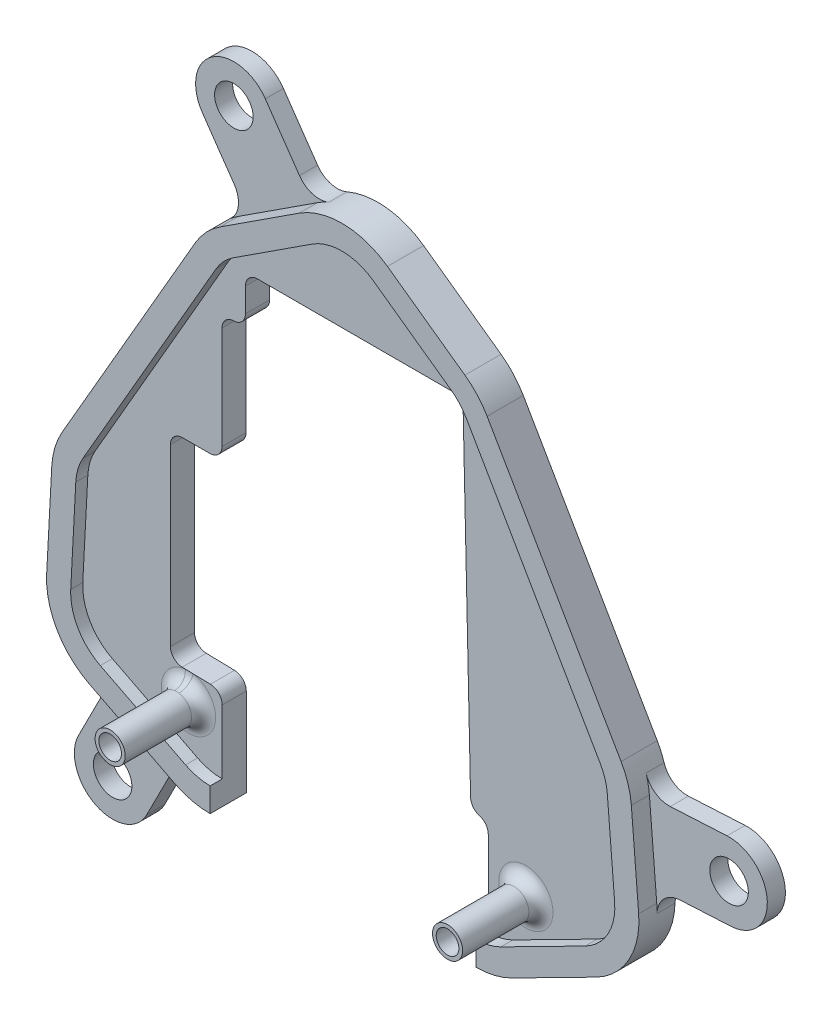
SolidWorks part; units mm, degrees
note: The reader was unsure of these and kept them because the rebuilt part matched: shared geometry of "Sketch2<4>", "Sketch2<7>".
ref_plane "Front" through (0, 0, 0) normal (0, 0, 1) x (1, 0, 0)
ref_plane "Top" through (0, 0, 0) normal (0, 1, 0) x (1, 0, 0)
ref_plane "Right" through (0, 0, 0) normal (1, 0, 0) x (0, 0, -1)
ref_plane "Plane1" through (0, 0, 5) normal (0, 0, 1) x (1, 0, 0)
sketch "Model" plane through (0, 0, 5) normal (0, 0, 1) x (1, 0, 0)
  line L0 (41.2744, 9.8256) -> (42.9744, 9.8256)
  line L1 (42.9744, 9.8256) -> (42.9744, 8.1256)
  line L2 (42.9744, 8.1256) -> (41.2744, 8.1256)
  line L3 (41.2744, 8.1256) -> (41.2744, 9.8256)
  line L4 (26.2031, 36.8727) -> (37.2177, 36.8727)
  line L5 (26.2031, 29.067) -> (26.2031, 36.8727)
  line L6 (26.2031, 29.067) -> (37.2177, 29.067)
  line L7 (37.2177, 29.067) -> (37.2177, 36.8727)
  line L8 (26.2031, 29.067) -> (26.2031, 36.8726)
  line L9 (26.2031, 36.8726) -> (37.2177, 36.8726)
  line L10 (37.2177, 36.8726) -> (37.2177, 29.067)
  line L11 (37.2177, 29.067) -> (26.2031, 29.067)
  line L12 (43.8871, 3.9834) -> (51.5741, 2.6279)
  line L13 (43.8871, 3.9834) -> (45.7997, 14.8306)
  line L14 (45.7997, 14.8306) -> (53.4867, 13.4752)
  line L15 (51.5741, 2.6279) -> (53.4867, 13.4752)
  line L16 (45.7997, 14.8306) -> (53.4868, 13.4752)
  line L17 (53.4868, 13.4752) -> (51.5741, 2.6279)
  line L18 (51.5741, 2.6279) -> (43.8871, 3.9834)
  line L19 (43.8871, 3.9834) -> (45.7997, 14.8306)
  line L20 (44.5033, 14.8869) -> (51.2631, 18.7897)
  line L21 (38.9959, 24.4258) -> (44.5033, 14.8869)
  line L22 (38.9959, 24.4258) -> (45.7558, 28.3286)
  line L23 (45.7558, 28.3286) -> (51.2631, 18.7897)
  line L24 (38.996, 24.4258) -> (45.7558, 28.3286)
  line L25 (45.7558, 28.3286) -> (51.2631, 18.7897)
  line L26 (51.2631, 18.7897) -> (44.5033, 14.8869)
  line L27 (44.5033, 14.8869) -> (38.996, 24.4258)
  line L28 (20.1071, -1.9033) -> (31.1217, -1.9033)
  line L29 (31.1217, -1.9033) -> (31.1217, 5.9022)
  line L30 (20.1071, 5.9022) -> (31.1217, 5.9022)
  line L31 (20.1071, -1.9033) -> (20.1071, 5.9022)
  line L32 (31.1217, 5.9022) -> (31.1217, -1.9033)
  line L33 (31.1217, -1.9033) -> (20.1071, -1.9033)
  line L34 (20.1071, -1.9033) -> (20.1071, 5.9023)
  line L35 (20.1071, 5.9023) -> (31.1217, 5.9022)
  line L36 (9.3055, 13.649) -> (16.9925, 15.0044)
  line L37 (16.9925, 15.0044) -> (18.9052, 4.1572)
  line L38 (11.2182, 2.8017) -> (18.9052, 4.1572)
  line L39 (9.3055, 13.649) -> (11.2182, 2.8017)
  line L40 (18.9052, 4.1571) -> (11.2182, 2.8017)
  line L41 (11.2182, 2.8017) -> (9.3055, 13.649)
  line L42 (9.3055, 13.649) -> (16.9925, 15.0044)
  line L43 (16.9925, 15.0044) -> (18.9052, 4.1571)
  line L44 (31.5611, -1.9033) -> (42.5757, -1.9033)
  line L45 (42.5757, -1.9033) -> (42.5757, 5.9022)
  line L46 (31.5611, 5.9022) -> (42.5757, 5.9022)
  line L47 (31.5611, -1.9033) -> (31.5611, 5.9022)
  line L48 (42.5757, 5.9022) -> (42.5757, -1.9033)
  line L49 (42.5757, -1.9033) -> (31.5611, -1.9033)
  line L50 (31.5611, -1.9033) -> (31.5611, 5.9023)
  line L51 (31.5611, 5.9023) -> (42.5757, 5.9022)
  line L52 (17.157, 27.6936) -> (23.9169, 23.7908)
  line L53 (18.4096, 14.2519) -> (23.9169, 23.7908)
  line L54 (11.6497, 18.1547) -> (18.4096, 14.2519)
  line L55 (11.6497, 18.1547) -> (17.157, 27.6936)
  line L56 (18.4096, 14.2519) -> (11.6497, 18.1547)
  line L57 (11.6497, 18.1547) -> (17.157, 27.6936)
  line L58 (17.157, 27.6936) -> (23.9169, 23.7908)
  line L59 (23.9169, 23.7908) -> (18.4096, 14.2519)
  line L60 (31.6641, -2.0303) -> (42.6787, -2.0303)
  line L61 (31.6641, -2.0303) -> (31.6641, 5.7752)
  line L62 (31.6641, 5.7752) -> (42.6787, 5.7752)
  line L63 (42.6787, -2.0303) -> (42.6787, 5.7752)
  line L64 (31.6641, 5.7752) -> (31.6641, -2.0303)
  line L65 (31.6641, -2.0303) -> (42.6787, -2.0303)
  line L66 (42.6787, -2.0303) -> (42.6787, 5.7753)
  line L67 (42.6787, 5.7753) -> (31.6641, 5.7752)
  line L68 (31.1217, -2.0304) -> (31.1217, 5.7752)
  line L69 (20.1071, 5.7752) -> (31.1217, 5.7752)
  line L70 (20.1071, -2.0304) -> (20.1071, 5.7752)
  line L71 (20.1071, -2.0304) -> (31.1217, -2.0304)
  line L72 (20.1071, 5.7752) -> (20.1071, -2.0304)
  line L73 (20.1071, -2.0304) -> (31.1217, -2.0304)
  line L74 (31.1217, -2.0304) -> (31.1217, 5.7752)
  line L75 (31.1217, 5.7752) -> (20.1071, 5.7752)
  line L76 (38.0604, 30.1846) -> (38.0604, 31.7086)
  line L77 (38.0604, 31.7086) -> (39.5844, 31.7086)
  line L78 (39.5844, 31.7086) -> (39.5844, 30.1846)
  line L79 (39.5844, 30.1846) -> (38.0604, 30.1846)
  line L80 (23.2104, 9.8646) -> (23.2104, 11.3886)
  line L81 (23.2104, 11.3886) -> (24.7344, 11.3886)
  line L82 (24.7344, 11.3886) -> (24.7344, 9.8646)
  line L83 (24.7344, 9.8646) -> (23.2104, 9.8646)
  line L84 (11.4952, 2.039) -> (18.4997, -1.5242)
  line L85 (10.454, 15.0927) -> (21.5718, 34.3494)
  line L86 (9.3219, 5.9287) -> (9.9312, 13.4171)
  line L87 (22.7072, 35.6017) -> (29.1341, 40.2036)
  line L88 (20.3133, -1.9589) -> (42.3955, -1.9589)
  line L89 (33.6436, 40.3046) -> (40.1911, 36.0465)
  line L90 (44.2091, -1.5242) -> (51.2858, 2.0757)
  line L91 (53.0458, 13.7815) -> (53.4666, 5.8529)
  line L92 (41.4745, 34.6932) -> (52.5155, 15.5695)
  circle A0 centre (31.7104, 23.1996) radius 1.4
  circle A1 centre (31.7104, 15.1997) radius 1.4
  circle A2 centre (42.1244, 16.5956) radius 0.85
  circle A3 centre (42.1244, 14.0556) radius 0.85
  circle A4 centre (42.1244, 11.5156) radius 0.85
  circle A5 centre (42.1244, 6.4356) radius 0.85
  circle A6 centre (26.2031, 36.8727) radius 0.0381
  circle A7 centre (37.2177, 36.8727) radius 0.0381
  circle A8 centre (26.2031, 29.067) radius 0.0381
  circle A9 centre (26.2031, 36.8727) radius 0.0381
  circle A10 centre (26.2031, 29.067) radius 0.0381
  circle A11 centre (37.2177, 29.067) radius 0.0381
  circle A12 centre (37.2177, 29.067) radius 0.0381
  circle A13 centre (37.2177, 36.8727) radius 0.0381
  circle A14 centre (43.8871, 3.9834) radius 0.0381
  circle A15 centre (51.5741, 2.6279) radius 0.0381
  circle A16 centre (43.8871, 3.9834) radius 0.0381
  circle A17 centre (45.7997, 14.8306) radius 0.0381
  circle A18 centre (45.7997, 14.8306) radius 0.0381
  circle A19 centre (53.4867, 13.4752) radius 0.0381
  circle A20 centre (51.5741, 2.6279) radius 0.0381
  circle A21 centre (53.4867, 13.4752) radius 0.0381
  circle A22 centre (44.5033, 14.8869) radius 0.0381
  circle A23 centre (51.2631, 18.7897) radius 0.0381
  circle A24 centre (38.9959, 24.4258) radius 0.0381
  circle A25 centre (44.5033, 14.8869) radius 0.0381
  circle A26 centre (38.9959, 24.4258) radius 0.0381
  circle A27 centre (45.7558, 28.3286) radius 0.0381
  circle A28 centre (45.7558, 28.3286) radius 0.0381
  circle A29 centre (51.2631, 18.7897) radius 0.0381
  circle A30 centre (20.1071, -1.9033) radius 0.0381
  circle A31 centre (31.1217, -1.9033) radius 0.0381
  circle A32 centre (31.1217, -1.9033) radius 0.0381
  circle A33 centre (31.1217, 5.9022) radius 0.0381
  circle A34 centre (20.1071, 5.9022) radius 0.0381
  circle A35 centre (31.1217, 5.9022) radius 0.0381
  circle A36 centre (20.1071, -1.9033) radius 0.0381
  circle A37 centre (20.1071, 5.9022) radius 0.0381
  circle A38 centre (9.3055, 13.649) radius 0.0381
  circle A39 centre (16.9925, 15.0044) radius 0.0381
  circle A40 centre (16.9925, 15.0044) radius 0.0381
  circle A41 centre (18.9052, 4.1572) radius 0.0381
  circle A42 centre (11.2182, 2.8017) radius 0.0381
  circle A43 centre (18.9052, 4.1572) radius 0.0381
  circle A44 centre (9.3055, 13.649) radius 0.0381
  circle A45 centre (11.2182, 2.8017) radius 0.0381
  circle A46 centre (31.5611, -1.9033) radius 0.0381
  circle A47 centre (42.5757, -1.9033) radius 0.0381
  circle A48 centre (42.5757, -1.9033) radius 0.0381
  circle A49 centre (42.5757, 5.9022) radius 0.0381
  circle A50 centre (31.5611, 5.9022) radius 0.0381
  circle A51 centre (42.5757, 5.9022) radius 0.0381
  circle A52 centre (31.5611, -1.9033) radius 0.0381
  circle A53 centre (31.5611, 5.9022) radius 0.0381
  circle A54 centre (17.157, 27.6936) radius 0.0381
  circle A55 centre (23.9169, 23.7908) radius 0.0381
  circle A56 centre (18.4096, 14.2519) radius 0.0381
  circle A57 centre (23.9169, 23.7908) radius 0.0381
  circle A58 centre (11.6497, 18.1547) radius 0.0381
  circle A59 centre (18.4096, 14.2519) radius 0.0381
  circle A60 centre (11.6497, 18.1547) radius 0.0381
  circle A61 centre (17.157, 27.6936) radius 0.0381
  circle A62 centre (31.6641, -2.0303) radius 0.0381
  circle A63 centre (42.6787, -2.0303) radius 0.0381
  circle A64 centre (31.6641, -2.0303) radius 0.0381
  circle A65 centre (31.6641, 5.7752) radius 0.0381
  circle A66 centre (31.6641, 5.7752) radius 0.0381
  circle A67 centre (42.6787, 5.7752) radius 0.0381
  circle A68 centre (42.6787, -2.0303) radius 0.0381
  circle A69 centre (42.6787, 5.7752) radius 0.0381
  circle A70 centre (31.1217, -2.0304) radius 0.0381
  circle A71 centre (31.1217, 5.7752) radius 0.0381
  circle A72 centre (20.1071, 5.7752) radius 0.0381
  circle A73 centre (31.1217, 5.7752) radius 0.0381
  circle A74 centre (20.1071, -2.0304) radius 0.0381
  circle A75 centre (20.1071, 5.7752) radius 0.0381
  circle A76 centre (20.1071, -2.0304) radius 0.0381
  circle A77 centre (31.1217, -2.0304) radius 0.0381
  circle A78 centre (23.9724, 20.7866) radius 0.762
  circle A79 centre (23.9724, 23.3266) radius 0.762
  circle A80 centre (23.9724, 25.8666) radius 0.762
  circle A81 centre (23.9724, 28.4066) radius 0.762
  circle A82 centre (23.9724, 30.9466) radius 0.762
  circle A83 centre (38.8224, 8.0866) radius 0.762
  circle A84 centre (38.8224, 10.6266) radius 0.762
  circle A85 centre (38.8224, 13.1666) radius 0.762
  circle A86 centre (38.8224, 15.7066) radius 0.762
  circle A87 centre (38.8224, 18.2466) radius 0.762
  circle A88 centre (38.8224, 20.7866) radius 0.762
  circle A89 centre (38.8224, 23.3266) radius 0.762
  circle A90 centre (38.8224, 25.8666) radius 0.762
  circle A91 centre (38.8224, 28.4066) radius 0.762
  circle A92 centre (23.9724, 18.2466) radius 0.762
  circle A93 centre (23.9724, 15.7066) radius 0.762
  circle A94 centre (23.9724, 13.1666) radius 0.762
  circle A95 centre (23.9724, 8.0866) radius 0.762
  circle A96 centre (11.4952, 2.039) radius 0.0032
  circle A97 centre (18.4997, -1.5242) radius 0.0032
  circle A98 centre (10.454, 15.0927) radius 0.0032
  circle A99 centre (21.5718, 34.3494) radius 0.0032
  circle A100 centre (9.3219, 5.9287) radius 0.0032
  circle A101 centre (9.9312, 13.4171) radius 0.0032
  circle A102 centre (22.7072, 35.6017) radius 0.0032
  circle A103 centre (29.1341, 40.2036) radius 0.0032
  circle A104 centre (20.3133, -1.9589) radius 0.0032
  circle A105 centre (42.3955, -1.9589) radius 0.0032
  circle A106 centre (33.6436, 40.3046) radius 0.0032
  circle A107 centre (40.1911, 36.0465) radius 0.0032
  circle A108 centre (44.2091, -1.5242) radius 0.0032
  circle A109 centre (51.2858, 2.0757) radius 0.0032
  circle A110 centre (53.0458, 13.7815) radius 0.0032
  circle A111 centre (53.4666, 5.8529) radius 0.0032
  circle A112 centre (41.4745, 34.6932) radius 0.0032
  circle A113 centre (52.5155, 15.5695) radius 0.0032
  arc A114 (9.3219, 5.9287) -> (11.4952, 2.039) centre (13.3088, 5.6042) ccw
  circle A115 centre (11.4951, 2.039) radius 0.0032
  circle A116 centre (9.3219, 5.9286) radius 0.0032
  arc A117 (33.6436, 40.3046) -> (29.1341, 40.2036) centre (31.4628, 36.9513) ccw
  circle A118 centre (29.1341, 40.2035) radius 0.0032
  circle A119 centre (33.6436, 40.3046) radius 0.0032
  arc A120 (10.454, 15.0927) -> (9.9312, 13.4171) centre (13.9181, 13.0927) ccw
  circle A121 centre (9.9312, 13.4171) radius 0.0032
  circle A122 centre (10.454, 15.0927) radius 0.0032
  arc A123 (22.7072, 35.6017) -> (21.5718, 34.3494) centre (25.036, 32.3495) ccw
  circle A124 centre (21.5718, 34.3494) radius 0.0032
  circle A125 centre (22.7072, 35.6017) radius 0.0032
  arc A126 (41.4745, 34.6932) -> (40.1911, 36.0465) centre (38.0104, 32.6932) ccw
  circle A127 centre (40.1911, 36.0464) radius 0.0032
  circle A128 centre (41.4745, 34.6932) radius 0.0032
  arc A129 (42.3955, -1.9589) -> (44.2091, -1.5242) centre (42.3955, 2.041) ccw
  circle A130 centre (44.2091, -1.5242) radius 0.0032
  circle A131 centre (42.3955, -1.959) radius 0.0032
  arc A132 (51.2858, 2.0757) -> (53.4666, 5.8529) centre (49.4722, 5.641) ccw
  circle A133 centre (53.4666, 5.8529) radius 0.0032
  circle A134 centre (51.2858, 2.0757) radius 0.0032
  arc A135 (53.0458, 13.7815) -> (52.5155, 15.5695) centre (49.0514, 13.5695) ccw
  circle A136 centre (52.5155, 15.5695) radius 0.0032
  circle A137 centre (53.0458, 13.7815) radius 0.0032
  arc A138 (18.4997, -1.5242) -> (20.3133, -1.9589) centre (20.3133, 2.041) ccw
  circle A139 centre (20.3133, -1.959) radius 0.0032
  circle A140 centre (18.4997, -1.5242) radius 0.0032
  circle A141 centre (45.1924, 1.6747) radius 1.5
  circle A142 centre (31.4564, 38.6936) radius 1.5
  circle A143 centre (17.1924, 1.6747) radius 1.5
sketch "Sketch2" plane through (0, 0, 5) normal (0, 0, 1) x (1, 0, 0)
  line L0 (21.9211, 34.9432) -> (39.9687, 34.9432)
  line L1 (39.9687, 34.9432) -> (40.6766, 3.3396)
  line L2 (40.6766, 3.3396) -> (15.6924, 3.9376)
  line L3 (15.6924, 3.9376) -> (15.6924, 20.4226)
  line L4 (15.6924, 20.4226) -> (19.972, 20.4226)
  line L5 (19.972, 20.4226) -> (19.972, 30.9408)
  line L6 (19.972, 30.9408) -> (21.9211, 30.9408)
  line L8 (21.9211, 30.9408) -> (21.9211, 34.9432)
  line L9 (42.0715, -2.4589) -> (19.9894, -2.4589) construction
  line L10 (51.1164, 1.5934) -> (44.1118, -1.9699) construction
  line L11 (52.952, 13.4576) -> (53.5613, 5.9692) construction
  line L12 (41.246, 34.5994) -> (52.3639, 15.3427) construction
  line L13 (33.5418, 40.6101) -> (39.9687, 36.0082) construction
  line L14 (21.9211, 36.4656) -> (28.4687, 40.7237) construction
  line L15 (9.4363, 15.8195) -> (20.4774, 34.9432) construction
  line L16 (8.419, 5.8794) -> (8.8398, 13.808) construction
  line L17 (17.9491, -1.9699) -> (10.8724, 1.6301) construction
  line L18 (41.1331, 37.6343) -> (34.7061, 42.2362)
  line L19 (54.0959, 16.3427) -> (42.9781, 35.5994)
  line L20 (55.5547, 6.1314) -> (54.9454, 13.6199)
  line L21 (45.0186, -3.7525) -> (52.0232, -0.1893)
  line L22 (19.9894, -4.4589) -> (42.0715, -4.4589)
  line L23 (9.9656, -0.1525) -> (17.0423, -3.7525)
  line L24 (6.8426, 13.914) -> (6.4218, 5.9854)
  line L25 (18.7453, 35.9432) -> (7.7042, 16.8195)
  line L26 (27.3783, 42.4004) -> (20.8308, 38.1423)
  line L27 (41.1331, 37.6343) -> (34.7061, 42.2362)
  line L28 (54.0959, 16.3427) -> (42.9781, 35.5994)
  line L29 (55.5547, 6.1314) -> (54.9454, 13.6199)
  line L30 (45.0186, -3.7525) -> (52.0232, -0.1893)
  line L31 (19.9894, -4.4589) -> (42.0715, -4.4589)
  line L32 (9.9656, -0.1525) -> (17.0423, -3.7525)
  line L33 (6.8426, 13.914) -> (6.4218, 5.9854)
  line L34 (18.7453, 35.9432) -> (7.7042, 16.8195)
  line L35 (27.3783, 42.4004) -> (20.8308, 38.1423)
  line L45 (42.0715, -2.4589) -> (19.9894, -2.4589)
  line L46 (51.1164, 1.5934) -> (44.1118, -1.9699)
  line L47 (52.952, 13.4576) -> (53.5613, 5.9692)
  line L48 (41.246, 34.5994) -> (52.3639, 15.3427)
  line L49 (33.5418, 40.6101) -> (39.9687, 36.0082)
  line L50 (21.9211, 36.4656) -> (28.4687, 40.7237)
  line L51 (9.4363, 15.8195) -> (20.4774, 34.9432)
  line L52 (8.419, 5.8794) -> (8.8398, 13.808)
  line L53 (17.9491, -1.9699) -> (10.8724, 1.6301)
  arc A0 (42.0715, -2.4589) -> (44.1118, -1.9699) centre (42.0716, 2.041) ccw construction
  arc A1 (51.1164, 1.5934) -> (53.5613, 5.9692) centre (49.0761, 5.6042) ccw construction
  arc A2 (23.0129, 23.4949) -> (20.6034, 19.3215) centre (22.3854, 21.075) ccw construction
  arc A16 (52.952, 13.4576) -> (52.3639, 15.3427) centre (48.4668, 13.0927) ccw construction
  arc A17 (41.246, 34.5994) -> (39.9687, 36.0082) centre (37.3489, 32.3495) ccw construction
  arc A18 (33.5418, 40.6101) -> (28.4687, 40.7237) centre (30.922, 36.9513) ccw construction
  arc A19 (21.9211, 36.4656) -> (20.4774, 34.9432) centre (24.3745, 32.6932) ccw construction
  arc A20 (9.4363, 15.8195) -> (8.8398, 13.808) centre (13.3334, 13.5695) ccw construction
  arc A21 (8.419, 5.8794) -> (10.8724, 1.6301) centre (12.9127, 5.641) ccw construction
  arc A22 (17.9491, -1.9699) -> (19.9894, -2.4589) centre (19.9893, 2.041) ccw construction
  arc A23 (42.9781, 35.5994) -> (41.1331, 37.6343) centre (37.3489, 32.3495) ccw
  arc A24 (54.9454, 13.6199) -> (54.0959, 16.3427) centre (48.4668, 13.0927) ccw
  arc A25 (52.0232, -0.1893) -> (55.5547, 6.1314) centre (49.0761, 5.6042) ccw
  arc A26 (42.0715, -4.4589) -> (45.0186, -3.7525) centre (42.0716, 2.041) ccw
  arc A27 (17.0423, -3.7525) -> (19.9894, -4.4589) centre (19.9893, 2.041) ccw
  arc A28 (6.4218, 5.9854) -> (9.9656, -0.1525) centre (12.9127, 5.641) ccw
  arc A29 (7.7042, 16.8195) -> (6.8426, 13.914) centre (13.3334, 13.5695) ccw
  arc A30 (20.8308, 38.1423) -> (18.7453, 35.9432) centre (24.3745, 32.6932) ccw
  arc A31 (34.7061, 42.2362) -> (27.3783, 42.4004) centre (30.922, 36.9513) ccw
  arc A32 (42.9781, 35.5994) -> (41.1331, 37.6343) centre (37.3489, 32.3495) ccw
  arc A33 (54.9454, 13.6199) -> (54.0959, 16.3427) centre (48.4668, 13.0927) ccw
  arc A34 (52.0232, -0.1893) -> (55.5547, 6.1314) centre (49.0761, 5.6042) ccw
  arc A35 (42.0715, -4.4589) -> (45.0186, -3.7525) centre (42.0716, 2.041) ccw
  arc A36 (17.0423, -3.7525) -> (19.9894, -4.4589) centre (19.9893, 2.041) ccw
  arc A37 (6.4218, 5.9854) -> (9.9656, -0.1525) centre (12.9127, 5.641) ccw
  arc A38 (7.7042, 16.8195) -> (6.8426, 13.914) centre (13.3334, 13.5695) ccw
  arc A39 (20.8308, 38.1423) -> (18.7453, 35.9432) centre (24.3745, 32.6932) ccw
  arc A40 (34.7061, 42.2362) -> (27.3783, 42.4004) centre (30.922, 36.9513) ccw
  arc A41 (42.0715, -2.4589) -> (44.1118, -1.9699) centre (42.0716, 2.041) ccw
  arc A42 (51.1164, 1.5934) -> (53.5613, 5.9692) centre (49.0761, 5.6042) ccw
  arc A43 (52.952, 13.4576) -> (52.3639, 15.3427) centre (48.4668, 13.0927) ccw
  arc A53 (41.246, 34.5994) -> (39.9687, 36.0082) centre (37.3489, 32.3495) ccw
  arc A54 (33.5418, 40.6101) -> (28.4687, 40.7237) centre (30.922, 36.9513) ccw
  arc A55 (21.9211, 36.4656) -> (20.4774, 34.9432) centre (24.3745, 32.6932) ccw
  arc A56 (9.4363, 15.8195) -> (8.8398, 13.808) centre (13.3334, 13.5695) ccw
  arc A57 (8.419, 5.8794) -> (10.8724, 1.6301) centre (12.9127, 5.641) ccw
  arc A58 (17.9491, -1.9699) -> (19.9894, -2.4589) centre (19.9893, 2.041) ccw
  circle A65 centre (17.1924, 1.6747) radius 0.9408 construction
  circle A66 centre (45.1924, 1.6747) radius 0.9408 construction
  circle A67 centre (17.1924, 1.6747) radius 0.9408
  circle A68 centre (45.1924, 1.6747) radius 0.9408
  circle A69 centre (45.1924, 1.6747) radius 1.25
  circle A70 centre (17.1924, 1.6747) radius 1.25
  dimension "D2" = 2.5
  dimension "D1" = 0
extrude "Boss-Extrude1" add sketch "Sketch2" along normal blind 2
extrude "Boss-Extrude3" add sketch "Sketch2<4>" along normal up to surface (3 mm away)
sketch "Sketch2<4>" plane through (0, 0, 5) normal (0, 0, 1) x (1, 0, 0) same geometry as "Sketch2"
extrude "Boss-Extrude4" add sketch "Sketch2<7>" along normal up to surface (8.5 mm away)
sketch "Sketch2<7>" plane through (0, 0, 5) normal (0, 0, 1) x (1, 0, 0) same geometry as "Sketch2"
sketch "Sketch3" plane through (0, 0, 5) normal (0, 0, -1) x (-1, 0, 0)
  line L0 (-57.4659, 7.3343) -> (-61.7249, 7.5604) construction
  line L1 (-61.3884, 13.9014) -> (-56.6794, 13.6515) construction
  line L2 (-17.847, 44.1006) -> (-20.4861, 40.2824) construction
  line L3 (-25.9016, 43.6153) -> (-23.0706, 47.7112) construction
  line L4 (-13.2245, -8.6704) -> (-15.1083, -4.9673) construction
  line L5 (-9.4976, -1.9915) -> (-7.5647, -5.7912) construction
  line L6 (-57.4659, 7.3343) -> (-61.7249, 7.5604)
  line L7 (-61.3884, 13.9014) -> (-56.6794, 13.6515)
  line L8 (-17.847, 44.1006) -> (-20.4861, 40.2824)
  line L9 (-25.9016, 43.6153) -> (-23.0706, 47.7112)
  line L10 (-13.2245, -8.6704) -> (-15.1083, -4.9673)
  line L11 (-9.4976, -1.9915) -> (-7.5647, -5.7912)
  line L12 (-8.938, 0.4978) -> (-17.6199, -4.0117)
  line L13 (-55.5729, 5.4) -> (-54.6659, 15.0473)
  line L14 (-20.1429, 37.6271) -> (-28.341, 42.9169)
  arc A0 (-55.5729, 5.4) -> (-57.4659, 7.3343) centre (-57.5719, 5.3372) ccw construction
  arc A1 (-61.3884, 13.9014) -> (-61.7249, 7.5604) centre (-61.5567, 10.7309) ccw construction
  arc A2 (-56.6794, 13.6515) -> (-54.6659, 15.0473) centre (-56.5734, 15.6487) ccw construction
  arc A3 (-28.341, 42.9169) -> (-25.9016, 43.6153) centre (-27.5469, 44.7525) ccw construction
  arc A4 (-20.4861, 40.2824) -> (-20.1429, 37.6271) centre (-18.8408, 39.1452) ccw construction
  arc A5 (-17.847, 44.1006) -> (-23.0706, 47.7112) centre (-20.4588, 45.9059) ccw construction
  circle A6 centre (-61.5567, 10.7309) radius 1.6 construction
  arc A7 (-15.1083, -4.9673) -> (-17.6199, -4.0117) centre (-16.8909, -5.8741) ccw construction
  arc A8 (-8.938, 0.4978) -> (-9.4976, -1.9915) centre (-7.715, -1.0847) ccw construction
  circle A9 centre (-10.3946, -7.2308) radius 1.6 construction
  arc A10 (-13.2245, -8.6704) -> (-7.5647, -5.7912) centre (-10.3946, -7.2308) ccw construction
  arc A11 (-55.5729, 5.4) -> (-57.4659, 7.3343) centre (-57.5719, 5.3372) ccw
  arc A12 (-61.3884, 13.9014) -> (-61.7249, 7.5604) centre (-61.5567, 10.7309) ccw
  arc A13 (-56.6794, 13.6515) -> (-54.6659, 15.0473) centre (-56.5734, 15.6487) ccw
  arc A14 (-28.341, 42.9169) -> (-25.9016, 43.6153) centre (-27.5469, 44.7525) ccw
  arc A15 (-20.4861, 40.2824) -> (-20.1429, 37.6271) centre (-18.8408, 39.1452) ccw
  arc A16 (-17.847, 44.1006) -> (-23.0706, 47.7112) centre (-20.4588, 45.9059) ccw
  circle A17 centre (-61.5567, 10.7309) radius 1.6
  arc A18 (-15.1083, -4.9673) -> (-17.6199, -4.0117) centre (-16.8909, -5.8741) ccw
  arc A19 (-8.938, 0.4978) -> (-9.4976, -1.9915) centre (-7.715, -1.0847) ccw
  circle A20 centre (-10.3946, -7.2308) radius 1.6
  arc A21 (-13.2245, -8.6704) -> (-7.5647, -5.7912) centre (-10.3946, -7.2308) ccw
  circle A22 centre (-20.4588, 45.9059) radius 1.6 construction
  circle A23 centre (-20.4588, 45.9059) radius 1.6
extrude "Boss-Extrude5" add sketch "Sketch3" against normal blind 1.5
fillet "Fillet3" radius 1 2 edges at (18.4424, 1.6747, 7) (46.4424, 1.6747, 7)
fillet "Fillet4" radius 1 7 edges at (15.6924, 3.9376, 6) (15.6924, 20.4226, 6) (19.972, 20.4226, 6) (21.9211, 30.9408, 6) (21.9211, 34.9432, 6) (39.9687, 34.9432, 6) (40.6766, 3.3396, 6)
fillet "Fillet5" radius 1 1 edges at (19.972, 30.9408, 6)
sketch "Sketch4" plane through (0, -4.4589, 0) normal (0, -1, 0) x (1, 0, 0)
  line L0 (42.0715, 8) -> (42.0715, 3.7397)
  line L1 (42.0715, 8) -> (42.0715, 5) construction
  line L2 (42.0715, 3.7397) -> (19.9894, 3.7397)
  line L3 (19.9894, 3.7397) -> (19.9894, 8)
  line L4 (19.9894, 8) -> (42.0715, 8)
  line L5 (19.9894, 13.5) -> (19.9894, 9.2) construction
  line L7 (42.0715, 8) -> (19.9894, 8) construction
extrude "Cut-Extrude1" cut sketch "Sketch4" against normal blind 10
fillet "Fillet6" radius 1 2 edges at (19.9894, 3.8347, 6) (40.6273, 5.5411, 6)
fillet "Fillet7" radius 1 1 edges at (42.0715, 5.5411, 6)
combine bodies "Combine1" operation type add bodies to combine 108 107
